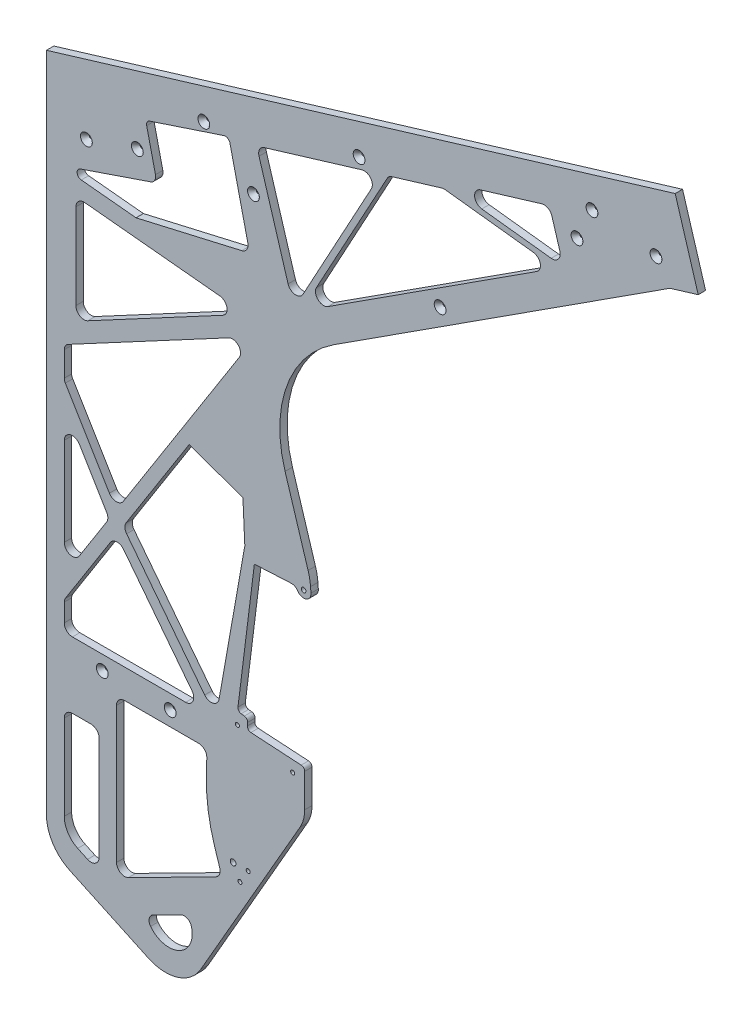
SolidWorks part; units mm, degrees
material "Beech"
ref_plane "Front Plane" through (0, 0, 0) normal (0, 0, 1) x (1, 0, 0)
ref_plane "Top Plane" through (0, 0, 0) normal (0, 1, 0) x (1, 0, 0)
ref_plane "Right Plane" through (0, 0, 0) normal (1, 0, 0) x (0, 0, -1)
sketch "Sketch1" plane through (0, 0, 0) normal (0, 0, 1) x (1, 0, 0)
  line L3 (-17.0528, -329.4943) -> (-52.061, -347.2658)
  line L9 (-123, -235.7894) -> (-123, -309.0696)
  line L10 (-100, -228.7894) -> (-116, -228.7894)
  line L11 (-93, -324.8124) -> (-93, -235.7894)
  line L12 (-111.4524, -327.1958) -> (-102.9583, -331.1566)
  line L20 (84, -200.7842) -> (84, -172.0664)
  line L21 (81.0197, -168.8973) -> (37.7062, -166.2368)
  line L23 (81.0197, -168.8973) -> (37.7062, -166.2368)
  line L24 (89.4313, -36.4853) -> (89.0709, -31.7487)
  line L25 (86.9733, -20.7388) -> (67.1502, 43.2142)
  line L39 (109.0999, 158.659) -> (398.6241, 345.5216)
  line L40 (398.6241, 345.5216) -> (422.935, 352.8794)
  line L46 (422.935, 352.8794) -> (403.0991, 418.4193)
  line L47 (403.0991, 418.4193) -> (-138.3789, 254.5381)
  line L48 (-138.3789, 254.5381) -> (-138.3789, -315.4534)
  line L49 (-118.2139, -347.1062) -> (-50.5059, -378.6789)
  line L50 (-5.4671, -364.4315) -> (80.009, -215.7351)
  line L55 (84, -200.7842) -> (84, -172.0664)
  line L62 (89.4313, -36.4853) -> (89.0709, -31.7487)
  line L63 (86.9733, -20.7388) -> (67.1502, 43.2142)
  line L64 (109.0999, 158.659) -> (398.6241, 345.5216)
  line L65 (398.6241, 345.5216) -> (422.935, 352.8794)
  line L66 (422.935, 352.8794) -> (403.0991, 418.4193)
  line L67 (403.0991, 418.4193) -> (-138.3789, 254.5381)
  line L68 (-138.3789, 254.5381) -> (-138.3789, -315.4534)
  line L69 (-61.1998, 168.1794) -> (29.8266, 189.1945)
  line L70 (-108.3476, 172.8251) -> (-61.1998, 168.1794)
  line L71 (-43.1791, 203.129) -> (-109.2468, 180.5917)
  line L72 (-52.0322, 241.4762) -> (-43.1791, 203.129)
  line L73 (14.4833, 267.3378) -> (-49.3928, 246.173)
  line L74 (35.0726, 197.5898) -> (19.6388, 264.4406)
  line L75 (-102.6958, 70.6213) -> (13.5473, 132.8622)
  line L76 (-113, 150.4873) -> (-113, 76.7923)
  line L77 (10.9295, 145.9995) -> (-105.3136, 157.4535)
  line L78 (-118.2139, -347.1062) -> (-50.5059, -378.6789)
  line L79 (-5.4671, -364.4315) -> (80.009, -215.7351)
  line L81 (-123, -28.6549) -> (-123, -104.7468)
  line L82 (-86.4916, -64.103) -> (-110.0027, -25.0448)
  line L83 (-110.0903, -108.4986) -> (-86.5792, -71.4649)
  line L91 (-78, -203.7894) -> (-78, -320.9929)
  line L92 (-7.2478, -196.7894) -> (-71, -196.7894)
  line L93 (-0.5975, -217.2122) -> (-0.2502, -203.9729)
  line L94 (10.9062, -280.6638) -> (6.4944, -266.8845)
  line L95 (-67.8314, -327.2347) -> (7.4081, -289.0401)
  line L97 (43.2335, -2.4917) -> (44.321, -25.8402) construction
  line L98 (69.3512, -23.7337) -> (62.886, 0.5467) construction
  line L99 (47.5047, -28.6948) -> (66.6392, -27.4998) construction
  line L107 (-15.4708, 21.8839) -> (-69.6883, -63.5168)
  line L108 (30.8453, 5.5646) -> (-15.4708, 21.8839)
  line L109 (32.4846, -29.6329) -> (30.8453, 5.5646)
  line L110 (10.3168, -155.1041) -> (32.4846, -29.6329)
  line L111 (-69.3092, -71.5595) -> (-2.1071, -158.1772)
  line L115 (-83.3585, -85.0495) -> (-123, -147.491)
  line L116 (-12.9629, -160.4984) -> (-71.9182, -84.5103)
  line L117 (-116, -171.7894) -> (-18.4936, -171.7894)
  line L118 (-123, -147.491) -> (-123, -164.7894)
  line L123 (18.5117, 118.5054) -> (-123, 42.7347)
  line L124 (-72.2002, -48.8158) -> (27.7256, 108.5825)
  line L125 (-123, 15.9373) -> (-84.1071, -48.674)
  line L126 (-123, 42.7347) -> (-123, 15.9373)
  line L166 (26.578, -152.854) -> (40.7015, -39.1783)
  line L183 (26.578, -152.854) -> (40.7015, -39.1783)
  line L184 (40.7015, -39.1783) -> (72.3075, -37.5674)
  line L185 (40.7015, -39.1783) -> (72.3075, -37.5674)
  line L240 (34.7318, -162.8731) -> (34.9029, -160.088)
  line L241 (34.7318, -162.8731) -> (34.9029, -160.088)
  line L242 (32.1253, -156.7426) -> (29.3373, -156.3962)
  line L243 (32.1253, -156.7426) -> (29.3373, -156.3962)
  circle A2 centre (83.098, -37.255) radius 2
  arc A4 (-52.061, -347.2658) -> (-17.0528, -329.4943) centre (-32.8243, -341.7931) ccw
  arc A20 (-123, -309.0696) -> (-111.4524, -327.1958) centre (-103, -309.0696) ccw
  arc A21 (-116, -228.7894) -> (-123, -235.7894) centre (-116, -235.7894) ccw
  arc A22 (-93, -235.7894) -> (-100, -228.7894) centre (-100, -235.7894) ccw
  arc A23 (-102.9583, -331.1566) -> (-93, -324.8124) centre (-100, -324.8124) ccw
  arc A31 (89.0709, -31.7487) -> (86.9733, -20.7388) centre (39.215, -35.5422) ccw
  arc A34 (109.0999, 158.659) -> (67.1502, 43.2142) centre (164.1952, 73.2946) ccw
  arc A35 (-138.3789, -315.4534) -> (-118.2139, -347.1062) centre (-103.4539, -315.4534) ccw
  arc A36 (-50.5059, -378.6789) -> (-5.4671, -364.4315) centre (-35.746, -347.0261) ccw
  arc A37 (80.009, -215.7351) -> (84, -200.7842) centre (54, -200.7842) ccw
  arc A46 (29.8266, 189.1945) -> (35.0726, 197.5898) centre (28.252, 196.0151) ccw
  arc A47 (-109.2468, 180.5917) -> (-108.3476, 172.8251) centre (-107.9554, 176.8059) ccw
  arc A48 (-49.3928, 246.173) -> (-52.0322, 241.4762) centre (-48.1347, 242.376) ccw
  arc A49 (19.6388, 264.4406) -> (14.4833, 267.3378) centre (15.7414, 263.5408) ccw
  arc A50 (89.0709, -31.7487) -> (86.9733, -20.7388) centre (39.215, -35.5422) ccw
  arc A51 (109.0999, 158.659) -> (67.1502, 43.2142) centre (164.1952, 73.2946) ccw
  arc A52 (13.5473, 132.8622) -> (10.9295, 145.9995) centre (10.2431, 139.0332) ccw
  arc A53 (-113, 76.7923) -> (-102.6958, 70.6213) centre (-106, 76.7923) ccw
  arc A54 (-105.3136, 157.4535) -> (-113, 150.4873) centre (-106, 150.4873) ccw
  arc A55 (-138.3789, -315.4534) -> (-118.2139, -347.1062) centre (-103.4539, -315.4534) ccw
  arc A56 (-50.5059, -378.6789) -> (-5.4671, -364.4315) centre (-35.746, -347.0261) ccw
  arc A57 (80.009, -215.7351) -> (84, -200.7842) centre (54, -200.7842) ccw
  arc A58 (-110.0027, -25.0448) -> (-123, -28.6549) centre (-116, -28.6549) ccw
  arc A59 (-86.5792, -71.4649) -> (-86.4916, -64.103) centre (-92.4888, -67.7131) ccw
  arc A60 (-123, -104.7468) -> (-110.0903, -108.4986) centre (-116, -104.7468) ccw
  arc A68 (-78, -320.9929) -> (-67.8314, -327.2347) centre (-71, -320.9929) ccw
  arc A69 (-71, -196.7894) -> (-78, -203.7894) centre (-71, -203.7894) ccw
  arc A70 (-0.2502, -203.9729) -> (-7.2478, -196.7894) centre (-7.2478, -203.7894) ccw
  arc A71 (-0.5975, -217.2122) -> (6.4944, -266.8845) centre (149.3509, -221.1459) ccw
  arc A72 (7.4081, -289.0401) -> (10.9062, -280.6638) centre (4.2395, -282.7983) ccw
  arc A74 (44.321, -25.8402) -> (47.5047, -28.6948) centre (47.3177, -25.7007) ccw construction
  arc A75 (62.886, 0.5467) -> (43.2335, -2.4917) centre (53.2227, -2.0264) ccw construction
  arc A76 (66.6392, -27.4998) -> (69.3512, -23.7337) centre (66.4522, -24.5056) ccw construction
  arc A78 (-69.6883, -63.5168) -> (-69.3092, -71.5595) centre (-63.7786, -67.2686) ccw
  arc A79 (-2.1071, -158.1772) -> (10.3168, -155.1041) centre (3.4235, -153.8863) ccw
  arc A84 (-71.9182, -84.5103) -> (-83.3585, -85.0495) centre (-77.4488, -88.8013) ccw
  arc A85 (-18.4936, -171.7894) -> (-12.9629, -160.4984) centre (-18.4936, -164.7894) ccw
  arc A86 (-123, -164.7894) -> (-116, -171.7894) centre (-116, -164.7894) ccw
  arc A88 (27.7256, 108.5825) -> (18.5117, 118.5054) centre (21.8159, 112.3343) ccw
  arc A89 (-84.1071, -48.674) -> (-72.2002, -48.8158) centre (-78.1098, -45.064) ccw
  arc A122 (84, -172.0664) -> (81.0197, -168.8973) centre (80.825, -172.0664) ccw
  arc A123 (84, -172.0664) -> (81.0197, -168.8973) centre (80.825, -172.0664) ccw
  arc A126 (77.9448, -40.4332) -> (83.5751, -43.2993) centre (83.2589, -36.9572) ccw
  arc A127 (77.9448, -40.4332) -> (83.5751, -43.2993) centre (83.2589, -36.9572) ccw
  arc A128 (83.5751, -43.2993) -> (89.4313, -36.4853) centre (83.0996, -36.9671) ccw
  arc A129 (83.5751, -43.2993) -> (89.4313, -36.4853) centre (83.0996, -36.9671) ccw
  arc A136 (77.9448, -40.4332) -> (72.3075, -37.5674) centre (72.6307, -43.9092) ccw
  arc A137 (77.9448, -40.4332) -> (72.3075, -37.5674) centre (72.6307, -43.9092) ccw
  arc A162 (34.7318, -162.8731) -> (37.7062, -166.2368) centre (37.9008, -163.0678) ccw
  arc A163 (34.7318, -162.8731) -> (37.7062, -166.2368) centre (37.9008, -163.0678) ccw
  arc A164 (34.9029, -160.088) -> (32.1253, -156.7426) centre (31.7338, -159.8934) ccw
  arc A165 (34.9029, -160.088) -> (32.1253, -156.7426) centre (31.7338, -159.8934) ccw
  arc A166 (26.578, -152.854) -> (29.3373, -156.3962) centre (29.7288, -153.2454) ccw
  arc A167 (26.578, -152.854) -> (29.3373, -156.3962) centre (29.7288, -153.2454) ccw
  line B0 (236.5506, 323.6498) -> (296.3216, 316.7428)
  line B1 (288.1657, 353.2968) -> (235.3263, 337.3033)
  line B2 (303.8249, 325.7244) -> (296.8934, 348.6248)
  line B3 (104.1239, 184.6459) -> (283.8662, 300.6596)
  line B4 (156.4343, 308.2003) -> (94.1802, 193.8748)
  line B5 (203.4752, 322.4386) -> (156.4343, 308.2003)
  line B6 (280.8737, 313.4946) -> (203.4752, 322.4386)
  line B7 (44.7058, 267.0687) -> (69.7399, 184.3604)
  line B8 (133.2777, 301.1913) -> (49.3777, 275.7965)
  line B9 (82.5874, 183.0407) -> (141.4532, 291.1438)
  arc B10 (296.3216, 316.7428) -> (303.8249, 325.7244) centre (297.1251, 323.6965) ccw
  arc B11 (235.3263, 337.3033) -> (236.5506, 323.6498) centre (237.3542, 330.6035) ccw
  arc B12 (296.8934, 348.6248) -> (288.1657, 353.2968) centre (290.1936, 346.5969) ccw
  arc B13 (283.8662, 300.6596) -> (280.8737, 313.4946) centre (280.0701, 306.5409) ccw
  arc B14 (94.1802, 193.8748) -> (104.1239, 184.6459) centre (100.3278, 190.5272) ccw
  arc B15 (69.7399, 184.3604) -> (82.5874, 183.0407) centre (76.4398, 186.3883) ccw
  arc B16 (49.3777, 275.7965) -> (44.7058, 267.0687) centre (51.4056, 269.0966) ccw
  arc B17 (141.4532, 291.1438) -> (133.2777, 301.1913) centre (135.3056, 294.4914) ccw
  dimension "D1" = 0
sketch_block_instance "Block1-1"
sketch_block "Block1"
extrude "Boss-Extrude1" add sketch "Sketch1" along normal blind 6.35
hole_wizard "#8 Clearance Hole1" positions "Sketch2" profile "Sketch3" hole size "#8" standard "ANSI Inch" end condition through all
sketch "Sketch2" plane through (0, 0, 6.35) normal (0, 0, 1) x (1, 0, 0)
  point P0 (22.4173, -270.7692)
sketch "Sketch3" plane through (22.4173, -270.7692, 6.35) normal (1, 0, 0) x (0, -1, 0)
  line L0 (0, 0) -> (0, 6.35)
  line L1 (0, 6.35) -> (2.4574, 6.35)
  line L2 (2.4574, 6.35) -> (2.4574, 0)
  line L5 (2.4574, 0) -> (0, 0)
  line L11 (0, -6.35) -> (0, 107.95) construction
  dimension "Thru Hole Dia." = 4.9149
  dimension "Thru Hole Depth" = 6.35
hole_wizard "#29 (0.136) Diameter Hole1" positions "Sketch4" profile "Sketch5" hole size "#29" standard "ANSI Inch" end condition through all
sketch "Sketch4" plane through (0, 0, 6.35) normal (0, 0, 1) x (1, 0, 0)
  point P0 (28.3036, -282.3356)
  point P5 (35.3953, -270.7692)
  point P9 (26.0849, -166.3788)
  point P12 (73.6862, -178.0913)
sketch "Sketch5" plane through (28.3036, -282.3356, 6.35) normal (1, 0, 0) x (0, -1, 0)
  line L0 (0, 0) -> (0, 6.35)
  line L1 (0, 6.35) -> (1.7272, 6.35)
  line L2 (1.7272, 6.35) -> (1.7272, 0)
  line L5 (1.7272, 0) -> (0, 0)
  line L11 (0, -6.35) -> (0, 107.95) construction
  dimension "Thru Hole Dia." = 3.4544
  dimension "Thru Hole Depth" = 6.35
fillet "Fillet2" radius 6.35 8 edges at (-52.061, -347.2658, 3.175) (-17.0528, -329.4943, 3.175) (-123, -147.491, 3.175) (-123, 15.9373, 3.175) (-123, 42.7347, 3.175) (-43.1791, 203.129, 3.175) (156.4343, 308.2003, 3.175) (203.4752, 322.4386, 3.175)
hole_wizard "Hole1" positions "Sketch6" profile "Sketch7" legacy
sketch "Sketch6" plane through (-277.2867, -215.2871, 6.35) normal (0, 0, 1) x (-0.09, -0.9959, 0)
  point P4 (-507.0387, 229.7761)
  point P6 (-559.3712, 359.3037)
  point P8 (-637.87, 553.5951)
  point P10 (-636.0712, 609.1114)
  point P12 (-609.4494, 543.2202)
  point P14 (-488.8705, 435.7568)
  point P16 (-478.4144, 275.2927)
  point P18 (-453.1036, 177.1887)
  point P20 (-434.4591, 134.8062)
  point P22 (-52.9605, 241.7526)
  point P24 (-47.6978, 183.4898)
sketch "Sketch7" plane through (-2.8292, 269.0251, 6.35) normal (1, 0, 0) x (0, -1, 0)
  line L0 (0, 0) -> (0, 32.7039)
  line L1 (0, 32.7039) -> (1.5875, 31.75)
  line L2 (1.5875, 31.75) -> (1.5875, 4.0177)
  line L3 (1.5875, 4.0177) -> (5.08, 0)
  line L4 (5.08, 0) -> (0, 0)
  line L5 (0, -14.3089) -> (0, 102.4216) construction
  line L6 (0, 32.7039) -> (-1.5875, 31.75) construction
  line L7 (-1.5875, 4.0177) -> (-5.08, 0) construction
  dimension "Diameter" = 3.175
  dimension "Depth" = 31.75
  dimension "C-Sink Diameter" = 10.16
  dimension "C-Sink Angle" = 82
  dimension "Drill Angle" = 118
